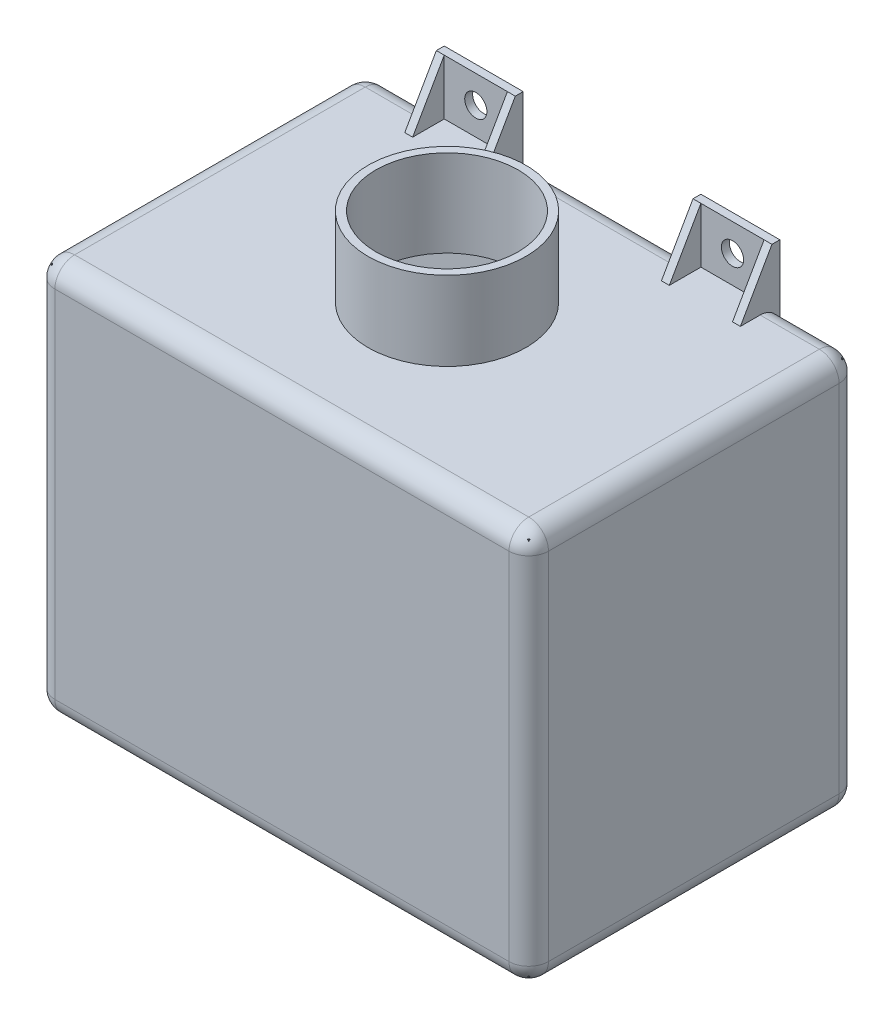
SolidWorks part; units mm, degrees
material "PE Low/Medium Density"
ref_plane "X-Y Datum" through (0, 0, 0) normal (0, 0, 1) x (1, 0, 0)
ref_plane "X-Z Datum" through (0, 0, 0) normal (0, 1, 0) x (1, 0, 0)
ref_plane "Y-Z Datum" through (0, 0, 0) normal (1, 0, 0) x (0, 0, -1)
sketch "Sketch1" plane through (0, 0, 0) normal (0, 1, 0) x (1, 0, 0)
  line L1 (79.375, 53.086) -> (-79.375, 53.086)
  line L2 (79.375, 53.086) -> (79.375, -53.086)
  line L3 (79.375, -53.086) -> (-79.375, -53.086)
  line L4 (-79.375, 53.086) -> (-79.375, -53.086)
  line L5 (79.375, 53.086) -> (-79.375, -53.086) construction
  line L6 (79.375, -53.086) -> (-79.375, 53.086) construction
  point P0 (0, 0)
  dimension "D1" = 158.75
  dimension "D2" = 106.172
extrude "Boss-Extrude1" add sketch "Sketch1" along normal blind 127
sketch "Sketch2" plane through (0, 127, 0) normal (0, 1, 0) x (1, 0, 0)
  circle A0 centre (0, 0) radius 25.4
  dimension "D1" = 50.8
extrude "Boss-Extrude2" add sketch "Sketch2" along normal blind 25.4
sketch "Sketch8" plane through (0, 0, 0) normal (0, -1, 0) x (1, 0, 0)
  line L0 (-79.375, 0) -> (79.375, 0)
  line L1 (-79.375, -53.086) -> (-79.375, 53.086) construction
  line L2 (79.375, 53.086) -> (79.375, -53.086) construction
  circle A0 centre (15.875, 0) radius 6.35
  dimension "D1" = 12.7
  dimension "D2" = 63.5
extrude "Boss-Extrude5" add sketch "Sketch8" along normal blind 30.48 contours A0
sketch "Sketch3" plane through (0, 127, 0) normal (0, 1, 0) x (1, 0, 0)
  line L0 (-53.975, 53.086) -> (-53.975, 40.386)
  line L1 (79.375, 53.086) -> (-79.375, 53.086) construction
  line L2 (-53.975, 40.386) -> (-51.435, 40.386)
  line L3 (-51.435, 40.386) -> (-51.435, 50.546)
  line L4 (-51.435, 50.546) -> (-31.115, 50.546)
  line L5 (-31.115, 50.546) -> (-31.115, 40.386)
  line L6 (-31.115, 40.386) -> (-28.575, 40.386)
  line L7 (-28.575, 40.386) -> (-28.575, 53.086)
  line L8 (-28.575, 53.086) -> (-53.975, 53.086)
  line L9 (-79.375, 53.086) -> (-79.375, -53.086) construction
  line L10 (0, 53.086) -> (0, -53.086) construction
  line L11 (-79.375, -53.086) -> (79.375, -53.086) construction
  line L12 (28.575, 53.086) -> (53.975, 53.086)
  line L13 (28.575, 40.386) -> (28.575, 53.086)
  line L14 (31.115, 40.386) -> (28.575, 40.386)
  line L15 (31.115, 50.546) -> (31.115, 40.386)
  line L16 (51.435, 50.546) -> (31.115, 50.546)
  line L17 (51.435, 40.386) -> (51.435, 50.546)
  line L18 (53.975, 40.386) -> (51.435, 40.386)
  line L19 (53.975, 53.086) -> (53.975, 40.386)
  dimension "D1" = 12.7
  dimension "D2" = 2.54
  dimension "D3" = 2.54
  dimension "D4" = 25.4
  dimension "D5" = 50.8
extrude "Boss-Extrude3" add sketch "Sketch3" along normal blind 17.78
sketch "Sketch5" plane through (31.115, 0, 0) normal (1, 0, 0) x (0, 0, -1)
  line L0 (40.386, 127) -> (50.546, 144.78)
  line L4 (40.386, 127) -> (50.546, 127)
  line L5 (50.546, 127) -> (50.546, 144.78)
  line L6 (50.546, 144.78) -> (40.386, 144.78)
  line L7 (40.386, 144.78) -> (40.386, 127)
  line L8 (40.386, 127) -> (50.546, 127)
  line L9 (50.546, 127) -> (50.546, 144.78)
  line L10 (50.546, 144.78) -> (40.386, 144.78)
  line L11 (40.386, 144.78) -> (40.386, 127)
  line M7 (50.546, 144.78) -> (40.386, 144.78)
  line M8 (40.386, 144.78) -> (40.386, 127)
  dimension "D1" = 0
extrude "Cut-Extrude2" cut sketch "Sketch5" against normal through all both and the other way through all contours L0 M8 M7 region at (31.115, 138.8533, -43.7727)
sketch "Sketch7" plane through (0, 0, 0) normal (0, -1, 0) x (1, 0, 0)
  line L0 (0, 53.086) -> (0, -53.086) construction
  line L1 (-79.375, 53.086) -> (79.375, 53.086) construction
  line L2 (79.375, -53.086) -> (-79.375, -53.086) construction
  line L3 (-15.24, -40.386) -> (-15.24, -53.086)
  line L4 (15.24, -40.386) -> (15.24, -53.086)
  line L5 (-15.24, -53.086) -> (15.24, -53.086)
  line L6 (-12.7, -40.386) -> (-12.7, -50.546)
  line L7 (12.7, -40.386) -> (12.7, -50.546)
  line L8 (-15.24, -40.386) -> (-12.7, -40.386)
  line L9 (-12.7, -50.546) -> (12.7, -50.546)
  line L10 (12.7, -40.386) -> (15.24, -40.386)
  line L11 (15.24, 53.086) -> (15.24, -53.086) construction
  line L12 (12.7, 53.086) -> (12.7, -53.086) construction
  line L13 (-12.7, 53.086) -> (-12.7, -53.086) construction
  line L14 (-15.24, 53.086) -> (-15.24, -53.086) construction
  line L15 (-15.24, -50.546) -> (15.24, -50.546) construction
  dimension "D5" = 12.7
  dimension "D6" = 2.54
  dimension "D1" = 15.24
  dimension "D2" = 15.24
  dimension "D3" = 12.7
  dimension "D4" = 12.7
extrude "Boss-Extrude4" add sketch "Sketch7" along normal blind 30.48
shell "Shell1" thickness 2.54 removed face at (0, 152.4, 25.4) removed face at (15.875, -30.48, -6.35)
sketch "Sketch9" plane through (-12.7, 0, 0) normal (1, 0, 0) x (0, 0, -1)
  line L5 (40.386, 0) -> (50.546, -30.48)
  line L10 (50.546, -30.48) -> (40.386, -30.48) construction
  line L11 (40.386, -30.48) -> (40.386, 0) construction
  line L12 (50.546, -30.48) -> (40.386, -30.48)
  line L13 (40.386, -30.48) -> (40.386, 0)
extrude "Cut-Extrude4" cut sketch "Sketch9" against normal through all both and the other way through all
hole_wizard "1/4 Clearance Hole1" positions "3DSketch1" profile "Sketch6" hole size "1/4" standard "ANSI Inch" end condition through all
sketch3d "3DSketch1"
  line L0 (-51.435, 144.78, -50.546) -> (-31.115, 127, -50.546)
  line L1 (31.115, 144.78, -50.546) -> (51.435, 127, -50.546)
  line L6 (12.7, -30.48, -50.546) -> (-12.7, -30.48, -50.546) construction
  line L7 (12.7, -30.48, -50.546) -> (12.7, 0, -50.546) construction
  point P0 (-41.275, 135.89, -50.546)
  point P10 (41.275, 135.89, -50.546)
  point P18 (0, -20.32, -50.546)
  dimension "D1" = 10.16
  dimension "D2" = 12.7
sketch "Sketch6" plane through (-41.275, 135.89, -50.546) normal (1, 0, 0) x (0, -1, 0)
  line L0 (0, 0) -> (0, 2.54)
  line L1 (0, 2.54) -> (3.5712, 2.54)
  line L2 (3.5712, 2.54) -> (3.5712, 0)
  line L5 (3.5712, 0) -> (0, 0)
  line L11 (0, -6.35) -> (0, 107.95) construction
  dimension "Thru Hole Dia." = 7.1425
  dimension "Thru Hole Depth" = 2.54
fillet "Fillet1" radius 6.35 15 edges at (79.375, 127, 0) (79.375, 63.5, -53.086) (79.375, 0, 0) (0, 127, 53.086) (79.375, 63.5, 53.086) (0, 0, 53.086) (-79.375, 63.5, -53.086) (-79.375, 127, 0) (-79.375, 63.5, 53.086) (-79.375, 0, 0) (-47.3075, 0, -53.086) (47.3075, 0, -53.086) (0, 127, -53.086) (-66.675, 127, -53.086) (66.675, 127, -53.086)
